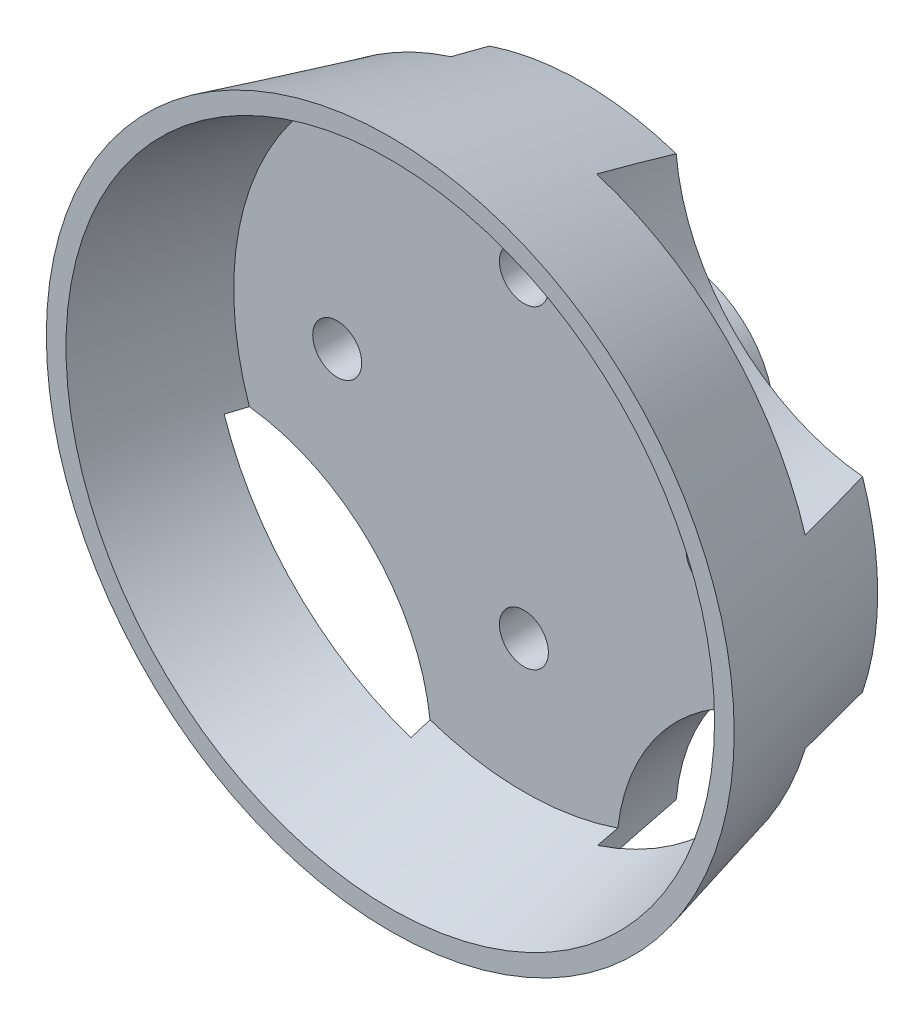
SolidWorks part; units mm, degrees
ref_plane "Спереди" through (0, 0, 0) normal (0, 0, 1) x (1, 0, 0)
ref_plane "Сверху" through (0, 0, 0) normal (0, 1, 0) x (1, 0, 0)
ref_plane "Справа" through (0, 0, 0) normal (1, 0, 0) x (0, 0, -1)
sketch "Эскиз1" plane through (0, 0, 0) normal (1, 0, 0) x (0, 0, -1)
  line L0 (0, 0) -> (8, 0)
  line L1 (8, 0) -> (8, 4.75)
  line L2 (8, 4.75) -> (3, 4.75)
  line L3 (3, 4.75) -> (3, 15)
  line L4 (3, 15) -> (-6.8, 17.5)
  line L5 (-6.8, 17.5) -> (-6.8, 16.5)
  line L6 (-6.8, 16.5) -> (0, 14.7653)
  line L7 (0, 14.7653) -> (0, 0)
  dimension "D1" = 15
  dimension "D2" = 4.75
  dimension "D3" = 5
  dimension "D4" = 3
  dimension "D5" = 9.8
  dimension "D6" = 16.5
  dimension "D7" = 17.5
revolve "Повернуть1" add sketch "Эскиз1" angle 360 about L0
sketch "Эскиз2" plane through (0, 0, -3) normal (0, 0, -1) x (-1, 0, 0)
  line L0 (-15.2028, -15.2028) -> (0, 0) construction
  line L1 (0, -8) -> (0, 0) construction
  circle A0 centre (0, 8) radius 1.245
  circle A1 centre (0, -8) radius 1.245
  circle A2 centre (9.5, 0) radius 1.245
  circle A3 centre (-9.5, 0) radius 1.245
  circle A4 centre (0, 0) radius 9.5 construction
  circle A5 centre (0, 0) radius 8 construction
  circle A6 centre (0, 0) radius 21.5 construction
  circle A7 centre (-15.2028, -15.2028) radius 10.5
  circle A8 centre (-15.2028, 15.2028) radius 10.5
  circle A9 centre (15.2028, 15.2028) radius 10.5 [skipped]
  circle A10 centre (15.2028, -15.2028) radius 10.5
  point P24 (0, 0)
  dimension "D1" = 2.49
  dimension "D2" = 16
  dimension "D3" = 19
  dimension "D4" = 21
  dimension "D5" = 43
  dimension "D6" = 45
  dimension "D7" = 4
extrude "Вырез-Вытянуть1" cut sketch "Эскиз2" against normal blind 4
sketch "Эскиз3" plane through (0, 0, -3) normal (0, 0, -1) x (-1, 0, 0)
  line L0 (15.2028, 15.2028) -> (0, 0) construction
  circle A0 centre (0, 0) radius 21.5 construction
  circle A1 centre (15.2028, 15.2028) radius 10.5
  arc A2 (-14.2287, 4.7481) -> (-4.7481, 14.2287) centre (-15.2028, 15.2028) ccw construction
  arc A3 (14.2287, -4.7481) -> (4.7481, -14.2287) centre (15.2028, -15.2028) ccw construction
  dimension "D1" = 43
  dimension "D2" = 21
extrude "Вырез-Вытянуть2" cut sketch "Эскиз3" against normal blind 2
scale "Масштаб1" scale about centroid uniform scaling yes scale factor 0.5
